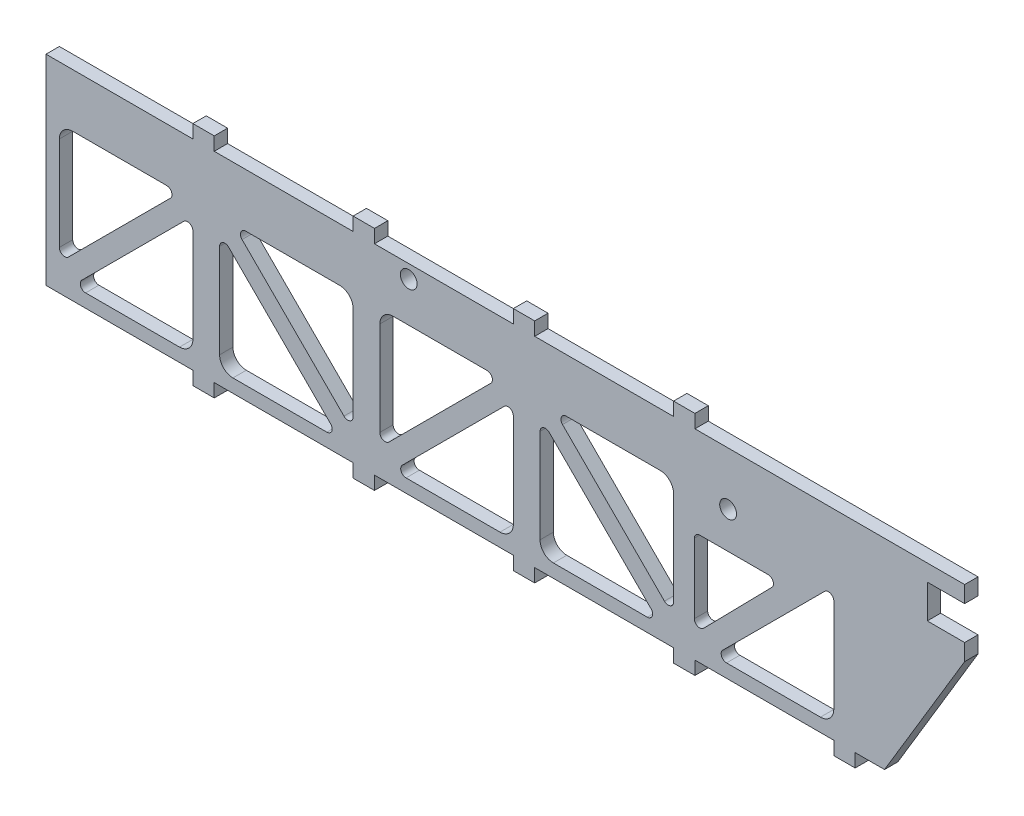
SolidWorks part; units mm, degrees
material "Pine"
ref_plane "Front Plane" through (0, 0, 0) normal (0, 0, 1) x (1, 0, 0)
ref_plane "Top Plane" through (0, 0, 0) normal (0, 1, 0) x (1, 0, 0)
ref_plane "Right Plane" through (0, 0, 0) normal (1, 0, 0) x (0, 0, -1)
sketch "Model" plane through (0, 0, 0) normal (0, 0, 1) x (1, 0, 0)
  line L0 (312.6855, 15.1239) -> (345.2281, 48.2988)
  line L1 (343.4149, 52.6175) -> (310.8722, 52.6175)
  line L2 (308.3322, 50.0775) -> (308.3322, 16.9026)
  line L8 (171.2321, 6.35) -> (215.9, 6.35)
  line L9 (217.9139, 59.1639) -> (169.4361, 10.6861)
  line L10 (222.25, 57.3679) -> (222.25, 12.7)
  line L11 (234.95, 57.3679) -> (234.95, 12.7)
  line L12 (239.2861, 59.1639) -> (287.7639, 10.6861)
  line L13 (241.3, 6.35) -> (285.9679, 6.35)
  line L14 (294.1139, 17.0361) -> (245.6361, 65.5139)
  line L15 (247.4321, 69.85) -> (292.1, 69.85)
  line L16 (298.45, 63.5) -> (298.45, 18.8321)
  line L17 (323.6321, 6.35) -> (368.3, 6.35)
  line L18 (370.3139, 59.1639) -> (321.8361, 10.6861)
  line L19 (374.65, 57.3679) -> (374.65, 12.7)
  line L20 (18.8321, 6.35) -> (63.5, 6.35)
  line L21 (17.0361, 10.6861) -> (65.5139, 59.1639)
  line L22 (69.85, 57.3679) -> (69.85, 12.7)
  line L23 (82.55, 57.3679) -> (82.55, 12.7)
  line L24 (86.8861, 59.1639) -> (135.3639, 10.6861)
  line L25 (88.9, 6.35) -> (133.5679, 6.35)
  line L26 (93.2361, 65.5139) -> (141.7139, 17.0361)
  line L27 (95.0321, 69.85) -> (139.7, 69.85)
  line L28 (146.05, 63.5) -> (146.05, 18.8321)
  line L29 (163.0861, 17.0361) -> (211.5639, 65.5139)
  line L30 (158.75, 63.5) -> (158.75, 18.8321)
  line L31 (165.1, 69.85) -> (209.7679, 69.85)
  line L35 (419.1, 87.376) -> (419.1, 71.374)
  line L36 (436.88, 87.376) -> (419.1, 87.376)
  line L37 (436.88, 87.376) -> (436.88, 95.25)
  line L38 (0, 95.25) -> (436.88, 95.25)
  line L39 (0, 0) -> (0, 95.25)
  line L40 (0, 0) -> (398.78, 0)
  line L41 (436.88, 63.5) -> (398.78, 0)
  line L42 (436.88, 63.5) -> (436.88, 71.374)
  line L43 (419.1, 71.374) -> (436.88, 71.374)
  line L44 (6.35, 63.5) -> (6.35, 18.8321)
  line L45 (12.7, 69.85) -> (57.3679, 69.85)
  line L46 (59.1639, 65.5139) -> (10.6861, 17.0361)
  arc A0 (215.9, 6.35) -> (222.25, 12.7) centre (215.9, 12.7) ccw
  arc A1 (169.4361, 10.6861) -> (171.2321, 6.35) centre (171.2321, 8.89) ccw
  arc A2 (222.25, 57.3679) -> (217.9139, 59.1639) centre (219.71, 57.3679) ccw
  arc A3 (239.2861, 59.1639) -> (234.95, 57.3679) centre (237.49, 57.3679) ccw
  arc A4 (285.9679, 6.35) -> (287.7639, 10.6861) centre (285.9679, 8.89) ccw
  arc A5 (234.95, 12.7) -> (241.3, 6.35) centre (241.3, 12.7) ccw
  arc A6 (247.4321, 69.85) -> (245.6361, 65.5139) centre (247.4321, 67.31) ccw
  arc A7 (298.45, 63.5) -> (292.1, 69.85) centre (292.1, 63.5) ccw
  arc A8 (294.1139, 17.0361) -> (298.45, 18.8321) centre (295.91, 18.8321) ccw
  arc A9 (321.8361, 10.6861) -> (323.6321, 6.35) centre (323.6321, 8.89) ccw
  arc A10 (374.65, 57.3679) -> (370.3139, 59.1639) centre (372.11, 57.3679) ccw
  arc A11 (368.3, 6.35) -> (374.65, 12.7) centre (368.3, 12.7) ccw
  arc A12 (63.5, 6.35) -> (69.85, 12.7) centre (63.5, 12.7) ccw
  arc A13 (17.0361, 10.6861) -> (18.8321, 6.35) centre (18.8321, 8.89) ccw
  arc A14 (69.85, 57.3679) -> (65.5139, 59.1639) centre (67.31, 57.3679) ccw
  arc A15 (86.8861, 59.1639) -> (82.55, 57.3679) centre (85.09, 57.3679) ccw
  arc A16 (133.5679, 6.35) -> (135.3639, 10.6861) centre (133.5679, 8.89) ccw
  arc A17 (82.55, 12.7) -> (88.9, 6.35) centre (88.9, 12.7) ccw
  arc A18 (95.0321, 69.85) -> (93.2361, 65.5139) centre (95.0321, 67.31) ccw
  arc A19 (146.05, 63.5) -> (139.7, 69.85) centre (139.7, 63.5) ccw
  arc A20 (141.7139, 17.0361) -> (146.05, 18.8321) centre (143.51, 18.8321) ccw
  arc A21 (158.75, 18.8321) -> (163.0861, 17.0361) centre (161.29, 18.8321) ccw
  arc A22 (165.1, 69.85) -> (158.75, 63.5) centre (165.1, 63.5) ccw
  arc A23 (211.5639, 65.5139) -> (209.7679, 69.85) centre (209.7679, 67.31) ccw
  arc A24 (345.2281, 48.2988) -> (343.4149, 52.6175) centre (343.4149, 50.0775) ccw
  arc A25 (310.8722, 52.6175) -> (308.3322, 50.0775) centre (310.8722, 50.0775) ccw
  arc A26 (312.6855, 15.1239) -> (308.3322, 16.9026) centre (310.8722, 16.9026) cw
  arc A27 (6.35, 18.8321) -> (10.6861, 17.0361) centre (8.89, 18.8321) ccw
  arc A28 (12.7, 69.85) -> (6.35, 63.5) centre (12.7, 63.5) ccw
  arc A29 (59.1639, 65.5139) -> (57.3679, 69.85) centre (57.3679, 67.31) ccw
  circle A30 centre (172.4917, 88.8013) radius 4
  circle A31 centre (324.3837, 70.0053) radius 4
  dimension "D2" = 6.4487
  dimension "D3" = 172.4917
  dimension "D4" = 8
  dimension "D5" = 18.796
  dimension "D6" = 8
  dimension "D8" = 2.54
  dimension "D1" = 95.25
  dimension "D7" = 151.892
extrude "Boss-Extrude2" add sketch "Model" along normal blind 6.35
sketch "Sketch1" plane through (0, 0, 6.35) normal (0, 0, 1) x (1, 0, 0)
  line L0 (69.85, 12.7) -> (69.85, 0) construction
  line L1 (146.05, 18.8321) -> (146.05, 0) construction
  line L2 (146.05, 18.8321) -> (146.05, 63.5) construction
  line L3 (0, 0) -> (398.78, 0) construction
  line L4 (222.25, 12.7) -> (222.25, 0) construction
  line L5 (222.25, 12.7) -> (222.25, 57.3679) construction
  line L6 (298.45, 18.8321) -> (298.45, 0) construction
  line L7 (146.05, 0) -> (156.21, 0)
  line L8 (69.85, 0) -> (80.01, 0)
  line L9 (69.85, 0) -> (69.85, -6.35)
  line L10 (69.85, -6.35) -> (80.01, -6.35)
  line L11 (80.01, 0) -> (80.01, -6.35)
  line L16 (222.25, 0) -> (232.41, 0)
  line L17 (222.25, 0) -> (222.25, -6.35)
  line L18 (222.25, -6.35) -> (232.41, -6.35)
  line L19 (232.41, 0) -> (232.41, -6.35)
  line L20 (146.05, 0) -> (146.05, -6.35)
  line L21 (146.05, -6.35) -> (156.21, -6.35)
  line L22 (156.21, 0) -> (156.21, -6.35)
  line L24 (374.65, 12.7) -> (374.65, 0) construction
  line L25 (374.65, 12.7) -> (374.65, 57.3679) construction
  line L26 (436.88, 95.25) -> (0, 95.25) construction
  line L27 (298.45, 0) -> (308.61, 0)
  line L28 (298.45, 0) -> (298.45, -6.35)
  line L29 (298.45, -6.35) -> (308.61, -6.35)
  line L30 (308.61, 0) -> (308.61, -6.35)
  line L31 (374.65, 0) -> (384.81, 0)
  line L32 (374.65, 0) -> (374.65, -6.35)
  line L33 (374.65, -6.35) -> (384.81, -6.35)
  line L34 (384.81, 0) -> (384.81, -6.35)
  line L35 (80.01, 95.25) -> (69.85, 95.25)
  line L36 (80.01, 95.25) -> (80.01, 101.6)
  line L37 (80.01, 101.6) -> (69.85, 101.6)
  line L38 (69.85, 95.25) -> (69.85, 101.6)
  line L40 (146.05, 95.25) -> (156.21, 95.25)
  line L41 (146.05, 95.25) -> (146.05, 101.6)
  line L42 (146.05, 101.6) -> (156.21, 101.6)
  line L43 (156.21, 95.25) -> (156.21, 101.6)
  line L44 (222.25, 95.25) -> (232.41, 95.25)
  line L45 (222.25, 95.25) -> (222.25, 101.6)
  line L46 (222.25, 101.6) -> (232.41, 101.6)
  line L47 (232.41, 95.25) -> (232.41, 101.6)
  line L48 (298.45, 95.25) -> (308.61, 95.25)
  line L49 (298.45, 95.25) -> (298.45, 101.6)
  line L50 (298.45, 101.6) -> (308.61, 101.6)
  line L51 (308.61, 95.25) -> (308.61, 101.6)
  arc A0 (368.3, 6.35) -> (374.65, 12.7) centre (368.3, 12.7) ccw construction
  dimension "D1" = 10.16
  dimension "D2" = 6.35
  dimension "D3" = 10.16
  dimension "D4" = 6.35
  dimension "D5" = 10.16
  dimension "D6" = 10.16
  dimension "D7" = 10.16
  dimension "D8" = 6.35
  dimension "D9" = 10.16
  dimension "D10" = 10.16
  dimension "D11" = 10.16
  dimension "D12" = 10.16
extrude "Boss-Extrude3" add sketch "Sketch1" against normal up to surface (6.35 mm away) up to face at (321.5295, 39.2174, 0)
